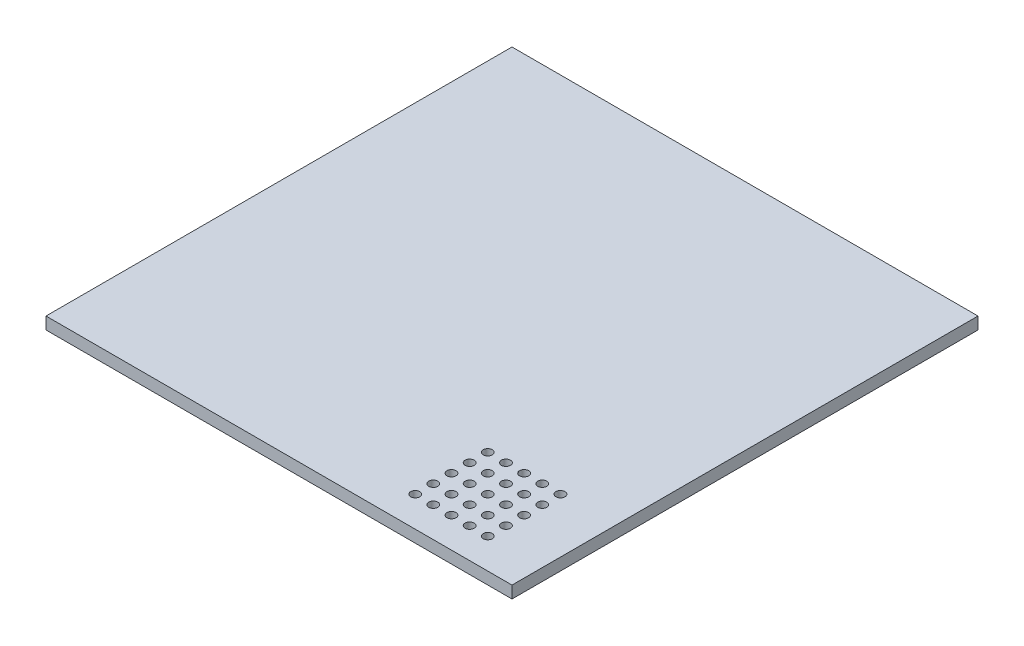
SolidWorks part; units mm, degrees
ref_plane "Front Plane" through (0, 0, 0) normal (0, 0, 1) x (1, 0, 0)
ref_plane "Top Plane" through (0, 0, 0) normal (0, 1, 0) x (1, 0, 0)
ref_plane "Right Plane" through (0, 0, 0) normal (1, 0, 0) x (0, 0, -1)
sketch "Sketch1" plane through (0, 0, 0) normal (0, 1, 0) x (1, 0, 0)
  line L0 (-47.5, 25.0543) -> (29.5, 25.0543) construction
  line L1 (29.5, 25.0543) -> (-9, 63.5543) construction
  line L2 (-9, -13.4457) -> (-9, -21.4272) construction
  line L3 (-47.5, 63.5543) -> (-47.5, -13.4457)
  line L4 (-47.5, 63.5543) -> (29.5, 63.5543)
  line L6 (-47.5, -13.4457) -> (29.5, -13.4457)
  line L7 (29.5, 63.5543) -> (29.5, -13.4457)
  line L13 (-46.2929, 62.3413) -> (-44.313, 60.3614) construction
  line L14 (-9, 63.5543) -> (-9, 25.0543) construction
  dimension "D1" = 77
  dimension "D2" = 38.5
extrude "Boss-Extrude1" add sketch "Sketch1" along normal blind 2
sketch "Sketch2" plane through (0, 2, 0) normal (0, 1, 0) x (1, 0, 0)
  line L0 (29.5, -13.4457) -> (29.5, 63.5543) construction
  line L1 (-47.5, -13.4457) -> (29.5, -13.4457) construction
  circle A0 centre (8.5, -8.4457) radius 0.75
  circle A1 centre (11.5, -8.4457) radius 0.75
  circle A2 centre (14.5, -8.4457) radius 0.75
  circle A3 centre (11.5, -5.4457) radius 0.75
  circle A4 centre (14.5, -5.4457) radius 0.75
  circle A5 centre (11.5, -2.4457) radius 0.75
  circle A6 centre (14.5, -2.4457) radius 0.75
  circle A7 centre (8.5, -5.4457) radius 0.75
  circle A8 centre (8.5, -2.4457) radius 0.75
  circle A9 centre (11.5, -8.4457) radius 0.75
  circle A10 centre (14.5, -8.4457) radius 0.75
  circle A11 centre (17.5, -8.4457) radius 0.75
  circle A12 centre (20.5, -8.4457) radius 0.75
  circle A13 centre (11.5, -5.4457) radius 0.75
  circle A14 centre (14.5, -5.4457) radius 0.75
  circle A15 centre (17.5, -5.4457) radius 0.75
  circle A16 centre (20.5, -5.4457) radius 0.75
  circle A17 centre (11.5, -2.4457) radius 0.75
  circle A18 centre (14.5, -2.4457) radius 0.75
  circle A19 centre (17.5, -2.4457) radius 0.75
  circle A20 centre (20.5, -2.4457) radius 0.75
  circle A21 centre (11.5, 0.5543) radius 0.75
  circle A22 centre (14.5, 0.5543) radius 0.75
  circle A23 centre (17.5, 0.5543) radius 0.75
  circle A24 centre (20.5, 0.5543) radius 0.75
  circle A25 centre (11.5, 3.5543) radius 0.75
  circle A26 centre (14.5, 3.5543) radius 0.75
  circle A27 centre (17.5, 3.5543) radius 0.75
  circle A28 centre (20.5, 3.5543) radius 0.75
  circle A29 centre (8.5, -5.4457) radius 0.75
  circle A30 centre (8.5, -2.4457) radius 0.75
  circle A31 centre (8.5, 0.5543) radius 0.75
  circle A32 centre (8.5, 3.5543) radius 0.75
  point P6 (0, 0)
  dimension "D1" = 1.5
  dimension "D2" = 21
  dimension "D3" = 5
  dimension "D4" = 3
  dimension "D5" = 3
  dimension "D6" = 5
  dimension "D7" = 5
extrude "Cut-Extrude1" cut sketch "Sketch2" against normal up to surface (2 mm away) contours A7 | A0 | A1 | A3 | A5 | A8 | A31 | A32 | A25 | A21 | A26 | A27 | A28 | A24 | A20 | A16 | A12 | A11 | A2 | A4 | A15 | A19 | A6 | A22 | A23 region at (8.5, 2, 8.4457) region at (11.5, 2, 8.4457) region at (14.5, 2, 8.4457) region at (11.5, 2, 5.4457) region at (14.5, 2, 5.4457) region at (11.5, 2, 2.4457) region at (14.5, 2, 2.4457) region at (8.5, 2, 5.4457) region at (8.5, 2, 2.4457) region at (17.5, 2, 8.4457) region at (20.5, 2, 8.4457) region at (17.5, 2, 5.4457) region at (20.5, 2, 5.4457) region at (17.5, 2, 2.4457) region at (20.5, 2, 2.4457) region at (11.5, 2, -0.5543) region at (14.5, 2, -0.5543) region at (17.5, 2, -0.5543) region at (20.5, 2, -0.5543) region at (11.5, 2, -3.5543) region at (14.5, 2, -3.5543) region at (17.5, 2, -3.5543) region at (20.5, 2, -3.5543) region at (8.5, 2, -0.5543) region at (8.5, 2, -3.5543) up to face at (-9, 0, -25.0543)
sketch "Sketch3" plane through (0, 0, 0) normal (0, -1, 0) x (1, 0, 0)
  line L0 (-47.5, -63.5543) -> (-47.5, 13.4457) construction
  line L1 (26, -60.0543) -> (-44, -60.0543)
  line L2 (26, -60.0543) -> (26, 9.9457)
  line L3 (26, 9.9457) -> (-44, 9.9457)
  line L4 (-44, -60.0543) -> (-44, 9.9457)
  line L5 (26, -60.0543) -> (-44, 9.9457) construction
  line L6 (26, 9.9457) -> (-44, -60.0543) construction
  line L7 (-47.5, 13.4457) -> (29.5, 13.4457) construction
  line L9 (24, -58.0543) -> (-42, -58.0543)
  line L10 (24, -58.0543) -> (24, 7.9457)
  line L11 (24, 7.9457) -> (-42, 7.9457)
  line L12 (-42, -58.0543) -> (-42, 7.9457)
  line L13 (24, -58.0543) -> (-42, 7.9457) construction
  line L14 (24, 7.9457) -> (-42, -58.0543) construction
  point P0 (-9, -25.0543)
  point P5 (-9, -25.0543)
  point P6 (-47.5, -25.0543)
  point P7 (-9, 13.4457)
  point P14 (-9, -25.0543)
  dimension "D1" = 70
  dimension "D2" = 70
  dimension "D3" = 2
extrude "Boss-Extrude2" add sketch "Sketch3" along normal blind 3
fillet "Fillet1" radius 0.5 8 edges at (26, -1.5, 9.9457) (26, -1.5, -60.0543) (26, -3, -25.0543) (-9, -3, 9.9457) (-44, -1.5, 9.9457) (-9, -3, -60.0543) (-44, -3, -25.0543) (-44, -1.5, -60.0543)
sketch "Sketch4" plane through (0, 0, -60.0543) normal (0, 0, -1) x (-1, 0, 0)
  line L1 (17, -2) -> (32, -2)
  line L2 (17, -2) -> (17, -3)
  line L3 (17, -3) -> (32, -3)
  line L4 (32, -2) -> (32, -3)
  line L5 (17, -2) -> (32, -3) construction
  line L6 (17, -3) -> (32, -2) construction
  line L8 (43.5, -3) -> (-25.5, -3) construction
  line L9 (47.5, 2) -> (47.5, 0) construction
  point P0 (24.5, -2.5)
  dimension "D1" = 1
  dimension "D2" = 15.5
  dimension "D3" = 15
extrude "Cut-Extrude2" cut sketch "Sketch4" against normal up to surface (2 mm away) up to face at (-9, -1.5, -58.0543)
